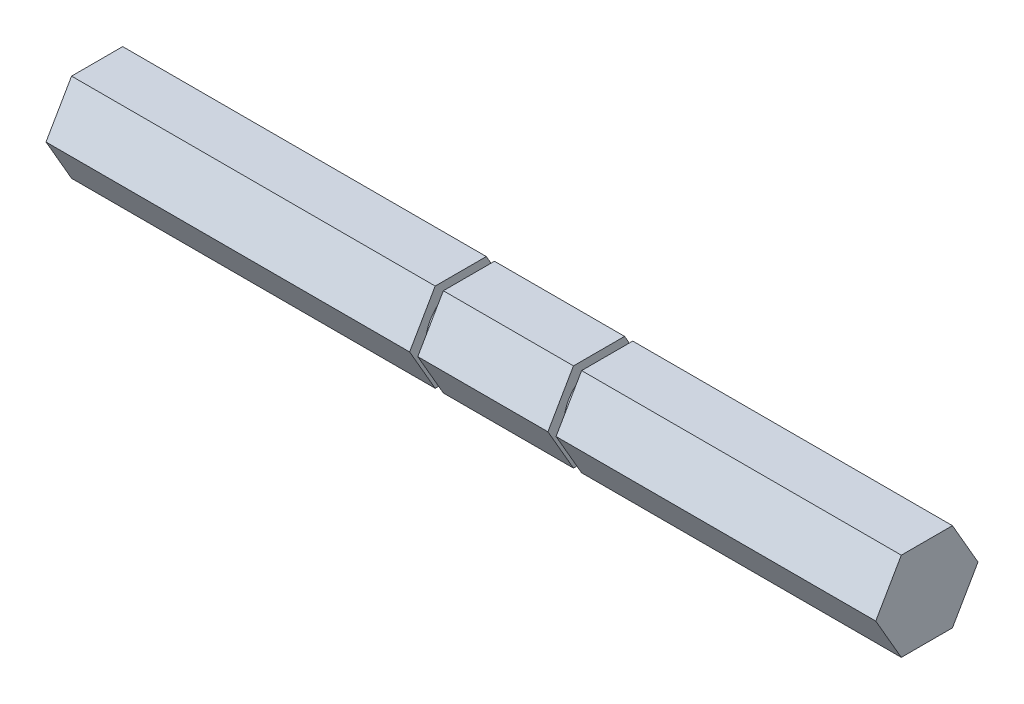
SolidWorks part; units mm, degrees
material "7075-T6 (SN)"
ref_plane "Front Plane" through (0, 0, 0) normal (0, 0, 1) x (1, 0, 0)
ref_plane "Top Plane" through (0, 0, 0) normal (0, 1, 0) x (1, 0, 0)
ref_plane "Right Plane" through (0, 0, 0) normal (1, 0, 0) x (0, 0, -1)
sketch "Sketch2" plane through (0, 0, 0) normal (1, 0, 0) x (0, 0, -1)
  line L1 (7.3323, 0) -> (3.6662, 6.35)
  line L2 (3.6662, 6.35) -> (-3.6662, 6.35)
  line L3 (-3.6662, 6.35) -> (-7.3323, 0)
  line L4 (-7.3323, 0) -> (-3.6662, -6.35)
  line L5 (-3.6662, -6.35) -> (3.6662, -6.35)
  line L6 (3.6662, -6.35) -> (7.3323, 0)
  circle A0 centre (0, 0) radius 6.35 construction
  dimension "D1" = 12.7
extrude "Boss-Extrude1" add sketch "Sketch2" along normal mid plane 119
sketch "Sketch5" plane through (0, 0, 0) normal (0, 0, 1) x (1, 0, 0)
  line L0 (0, 0) -> (66.5467, 0) construction
  line L1 (12.4816, 13.9685) -> (13.65, 13.9685)
  line L2 (12.4816, 13.9685) -> (12.4816, 5.0292)
  line L3 (12.4816, 5.0292) -> (13.65, 5.0292)
  line L4 (13.65, 13.9685) -> (13.65, 5.0292)
  line L5 (59.5, 6.35) -> (59.5, 0) construction
  line L6 (-7.35, 13.9685) -> (-7.35, 5.0292)
  line L7 (-7.35, 13.9685) -> (-6.1816, 13.9685)
  line L8 (-6.1816, 13.9685) -> (-6.1816, 5.0292)
  line L9 (-7.35, 5.0292) -> (-6.1816, 5.0292)
  dimension "D1" = 1.1684
  dimension "D2" = 10.0584
  dimension "D3" = 45.85
  dimension "D5" = 21
  dimension "D4" = 2
revolve "Cut-Revolve1" cut sketch "Sketch5" angle 360 about L0
ref_axis "Axis1" through (55.0595, 0, 0) along (-1, 0, 0)
